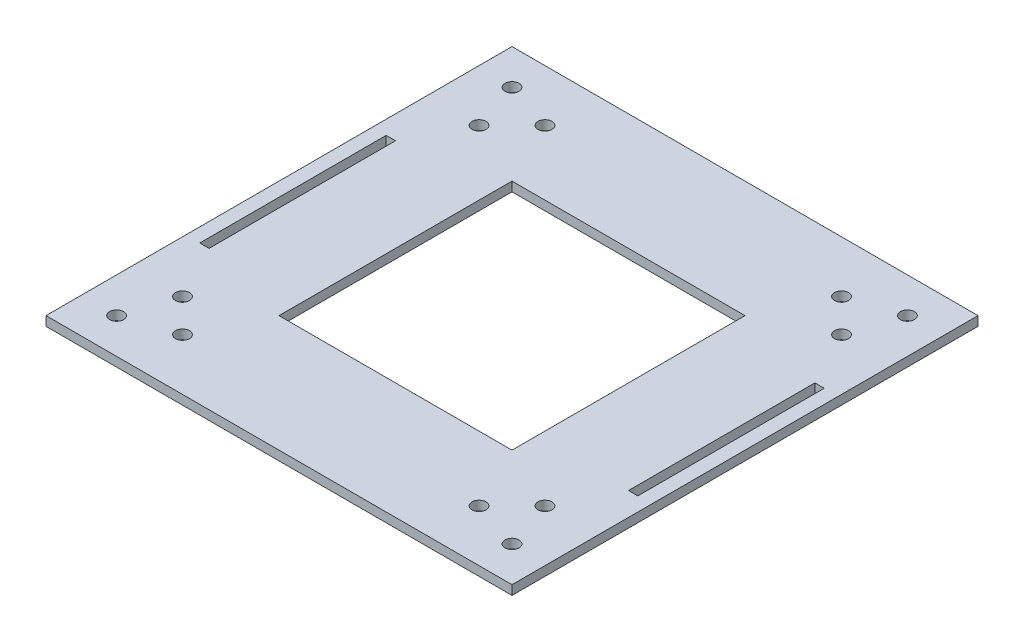
SolidWorks part; units mm, degrees
material "Thornel Mat VMA"
ref_plane "前视基准面" through (0, 0, 0) normal (0, 0, 1) x (1, 0, 0)
ref_plane "上视基准面" through (0, 0, 0) normal (0, 1, 0) x (1, 0, 0)
ref_plane "右视基准面" through (0, 0, 0) normal (1, 0, 0) x (0, 0, -1)
other "Configuration Table"
sketch "草图1" plane through (0, 0, 0) normal (0, 1, 0) x (1, 0, 0)
  line L1 (-50, -50) -> (50, -50)
  line L2 (-50, -50) -> (-50, 50)
  line L3 (-50, 50) -> (50, 50)
  line L4 (50, -50) -> (50, 50)
  line L5 (-50, -50) -> (50, 50) construction
  line L6 (-50, 50) -> (50, -50) construction
  point P0 (0, 0)
  dimension "D1" = 100
  dimension "D2" = 100
extrude "凸台-拉伸1" add sketch "草图1" along normal blind 2
sketch "草图3" plane through (0, 2, 0) normal (0, 1, 0) x (1, 0, 0)
  line L0 (-1000, 0) -> (49000, 0) construction
  line L1 (-42.4264, 42.4264) -> (0, 0) construction
  line L2 (-42.9749, 27.7358) -> (35312.3642, 35383.0749) construction
  line L3 (0, -1000) -> (0, 49000) construction
  circle A0 centre (0, 0) radius 60 construction
  circle A1 centre (-42.4264, 42.4264) radius 1.5
  circle A2 centre (-31.8198, 38.8909) radius 1.5
  circle A3 centre (-38.8909, 31.8198) radius 1.5
  circle A4 centre (-31.8198, -38.8909) radius 1.5
  circle A5 centre (-38.8909, -31.8198) radius 1.5
  circle A6 centre (-42.4264, -42.4264) radius 1.5
  circle A7 centre (31.8198, 38.8909) radius 1.5
  circle A8 centre (38.8909, 31.8198) radius 1.5
  circle A9 centre (42.4264, 42.4264) radius 1.5
  circle A10 centre (31.8198, -38.8909) radius 1.5
  circle A11 centre (42.4264, -42.4264) radius 1.5
  circle A12 centre (38.8909, -31.8198) radius 1.5
  dimension "D1" = 120
  dimension "D3" = 3
  dimension "D6" = 3
  dimension "D7" = 3
  dimension "D8" = 5
  dimension "D9" = 5
  dimension "D2" = 45
  dimension "D4" = 90
  dimension "D5" = 10
extrude "切除-拉伸2" cut sketch "草图3" against normal through all
sketch "草图4" plane through (0, 2, 0) normal (0, 1, 0) x (1, 0, 0)
  line L1 (-25, -25) -> (25, -25)
  line L2 (-25, -25) -> (-25, 25)
  line L3 (-25, 25) -> (25, 25)
  line L4 (25, -25) -> (25, 25)
  line L5 (-25, -25) -> (25, 25) construction
  line L6 (-25, 25) -> (25, -25) construction
  point P0 (0, 0)
  dimension "D1" = 50
  dimension "D2" = 50
extrude "切除-拉伸3" cut sketch "草图4" against normal through all
sketch "草图5" plane through (0, 2, 0) normal (0, 1, 0) x (1, 0, 0)
  line L0 (-50, 50) -> (-50, -50) construction
  line L1 (-47, -20) -> (-45, -20)
  line L2 (-47, -20) -> (-47, 20)
  line L3 (-47, 20) -> (-45, 20)
  line L4 (-45, -20) -> (-45, 20)
  line L5 (-47, -20) -> (-45, 20) construction
  line L6 (-47, 20) -> (-45, -20) construction
  line L7 (0, -1000) -> (0, 49000) construction
  line L8 (47, -20) -> (45, -20)
  line L9 (47, 20) -> (45, 20)
  line L10 (45, -20) -> (45, 20)
  line L11 (47, -20) -> (47, 20)
  point P0 (-46, 0)
  dimension "D1" = 40
  dimension "D2" = 2
  dimension "D3" = 3
  dimension "D4" = 0
extrude "切除-拉伸4" cut sketch "草图5" against normal through all
